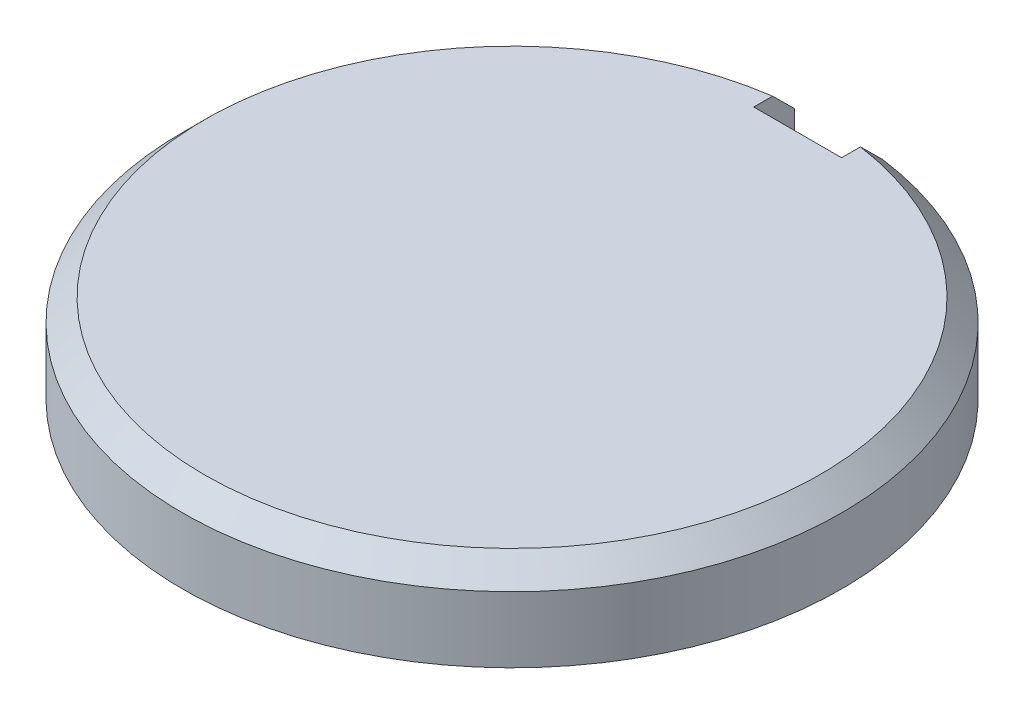
SolidWorks part; units mm, degrees
ref_plane "Front Plane" through (0, 0, 0) normal (0, 0, 1) x (1, 0, 0)
ref_plane "Top Plane" through (0, 0, 0) normal (0, 1, 0) x (1, 0, 0)
ref_plane "Right Plane" through (0, 0, 0) normal (1, 0, 0) x (0, 0, -1)
ref_plane "Plane1" through (0, 0, -62) normal (0, 0, 1) x (1, 0, 0)
sketch "Sketch1" plane through (0, 0, -62) normal (0, 0, 1) x (1, 0, 0)
  line L0 (0, 44.4) -> (0, 57.2) construction
  line L1 (2.3, 49.4) -> (2.3, 50.6)
  line L2 (2.3, 50.6) -> (0, 50.6)
  line L3 (0, 50.6) -> (0, 52.2)
  line L4 (0, 52.2) -> (5.6, 52.2)
  line L5 (5.6, 52.2) -> (6, 51.8)
  line L6 (6, 51.8) -> (6, 50.6)
  line L7 (6, 50.6) -> (3, 50.6)
  line L8 (3, 50.6) -> (3, 49.4)
  line L9 (3, 49.4) -> (2.3, 49.4)
revolve "Revolve1" add sketch "Sketch1" angle 360 about L0
sketch "Sketch2" plane through (0, 0, 0) normal (0, 0, 1) x (1, 0, 0)
  line L1 (-0.4, 49.3) -> (0.4, 49.3)
  line L2 (-0.4, 49.3) -> (-0.4, 50.58)
  line L3 (-0.4, 50.58) -> (0.4, 50.58)
  line L4 (0.4, 49.3) -> (0.4, 50.58)
extrude "Boss-Extrude1" add sketch "Sketch2" along normal blind 6.4 from offset 65.2 separate body offset against normal yes
combine bodies "Combine1" operation type subtract main body 101 bodies to subtract 102
sketch "Sketch3" plane through (0, 0, 0) normal (0, 0, 1) x (1, 0, 0)
  line L1 (-3.2, 49.3) -> (3.2, 49.3)
  line L2 (-3.2, 49.3) -> (-3.2, 50.58)
  line L3 (-3.2, 50.58) -> (3.2, 50.58)
  line L4 (3.2, 49.3) -> (3.2, 50.58)
extrude "Boss-Extrude2" add sketch "Sketch3" along normal blind 0.8 from offset 62.4 separate body offset against normal yes
combine bodies "Combine2" operation type subtract main body 103 bodies to subtract 104
sketch "Sketch4" plane through (0, 0, 0) normal (0, 0, 1) x (1, 0, 0)
  line L1 (-0.8, 50.5) -> (0.8, 50.5)
  line L2 (-0.8, 50.5) -> (-0.8, 52.3)
  line L3 (-0.8, 52.3) -> (0.8, 52.3)
  line L4 (0.8, 50.5) -> (0.8, 52.3)
extrude "Boss-Extrude3" add sketch "Sketch4" along normal blind 0.9 from offset 68.1 separate body offset against normal yes
combine bodies "Combine3" operation type subtract main body 105 bodies to subtract 106
